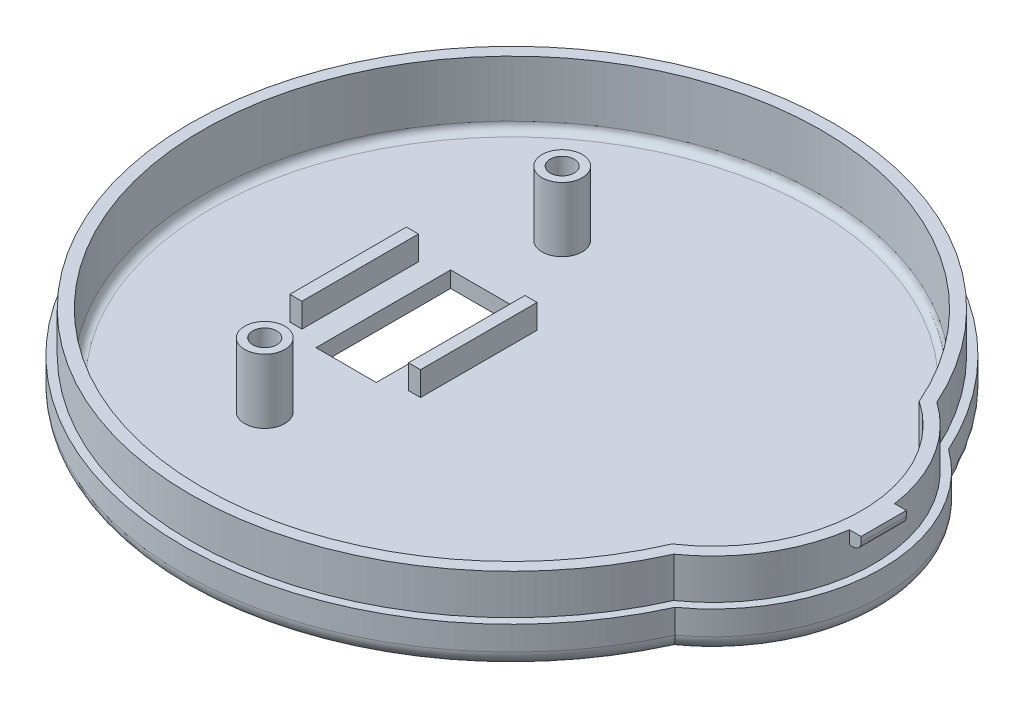
SolidWorks part; units mm, degrees
ref_plane "Front Plane" through (0, 0, 0) normal (0, 0, 1) x (1, 0, 0)
ref_plane "Top Plane" through (0, 0, 0) normal (0, 1, 0) x (1, 0, 0)
ref_plane "Right Plane" through (0, 0, 0) normal (1, 0, 0) x (0, 0, -1)
sketch "Sketch4" plane through (0, 0, 0) normal (0, 1, 0) x (1, 0, 0)
  line L0 (0, 0) -> (25, 0)
  line L1 (-47.85, 0) -> (47.85, 0) construction
  arc A0 (36.5, 16.3631) -> (36.5, -16.3631) centre (0, 0) ccw
  arc A1 (36.5, -16.3631) -> (36.5, 16.3631) centre (25, 0) ccw
  arc A2 (36.5, 16.3631) -> (5, 0) centre (25, 0) ccw construction
  arc A3 (5, 0) -> (36.5, -16.3631) centre (25, 0) ccw construction
  arc A4 (36.5, -16.3631) -> (36.5, 16.3631) centre (0, 0) ccw construction
  arc A5 (37.3, 17.0209) -> (37.3, -17.0209) centre (0, 0) ccw
  arc A6 (37.3, -17.0209) -> (37.3, 17.0209) centre (25, 0) ccw
  arc A7 (35.3, 15.3675) -> (35.3, -15.3675) centre (0, 0) ccw
  arc A8 (35.3, -15.3675) -> (35.3, 15.3675) centre (25, 0) ccw
  point P16 (0, 0)
  point P17 (0, 0)
  dimension "D1" = 80
  dimension "D2" = 40
  dimension "D3" = 25
  dimension "D4" = 1
  dimension "D5" = 2.5
extrude "Boss-Extrude3" add sketch "Sketch4" along normal blind 2 contours A7 A8 | A0 A1 A8 A7 | A5 A6 A1 A0 region at (43.8327, 0, 0) region at (45.8804, 0, 0) region at (42.3751, 0, 0)
extrude "Boss-Extrude4" add sketch "Sketch4<5>" along normal blind 10 contours A0 A1 A8 A7 region at (43.8327, 0, 0)
sketch "Sketch4<5>" plane through (0, 0, 0) normal (0, 1, 0) x (1, 0, 0) same geometry as "Sketch4"
extrude "Boss-Extrude5" add sketch "Sketch4<6>" along normal blind 5 contours A5 A6 A1 A0 region at (45.8804, 0, 0)
sketch "Sketch4<6>" plane through (0, 0, 0) normal (0, 1, 0) x (1, 0, 0) same geometry as "Sketch4"
sketch "Sketch11" plane through (0, 10, 0) normal (0, 1, 0) x (1, 0, 0)
  line L1 (43.75, -2.8061) -> (46.25, -2.8061)
  line L2 (43.75, -2.8061) -> (43.75, 2.8061)
  line L3 (43.75, 2.8061) -> (46.25, 2.8061)
  line L4 (46.25, -2.8061) -> (46.25, 2.8061)
  line L5 (43.75, -2.8061) -> (46.25, 2.8061) construction
  line L6 (43.75, 2.8061) -> (46.25, -2.8061) construction
  arc A0 (36.5, -16.3631) -> (36.5, 16.3631) centre (25, 0) ccw construction
  point P0 (45, 0)
  dimension "D1" = 2.5
extrude "Boss-Extrude7" add sketch "Sketch11" against normal blind 1.65
fillet "Fillet2" radius 1 1 edges at (46.25, 8.35, 0)
sketch "Sketch12" plane through (0, 0, 0) normal (0, -1, 0) x (1, 0, 0)
  line L0 (-41, 0) -> (-12.25, 0)
  line L1 (47.85, 0) -> (-47.85, 0) construction
  line L7 (-16, -8.375) -> (-8.5, -8.375)
  line L8 (-16, -8.375) -> (-16, 8.375)
  line L9 (-16, 8.375) -> (-8.5, 8.375)
  line L10 (-8.5, -8.375) -> (-8.5, 8.375)
  line L11 (-16, -8.375) -> (-8.5, 8.375) construction
  line L12 (-16, 8.375) -> (-8.5, -8.375) construction
  arc A0 (37.3, 17.0209) -> (37.3, -17.0209) centre (0, 0) ccw construction
  dimension "D1" = 28.75
  dimension "D2" = 16.75
  dimension "D3" = 7.5
extrude "Cut-Extrude1" cut sketch "Sketch12" against normal up to surface (2 mm away) contours L8 L9 L10 L7 up to face at (2.5, 2, 0)
sketch "Sketch15" plane through (0, 0, 0) normal (0, -1, 0) x (1, 0, 0)
  line L0 (-8.5, 8.375) -> (-10.6212, 8.375)
  line L1 (-16, 8.375) -> (-8.5, 8.375) construction
  line L2 (-10.6212, 8.375) -> (-10.6212, 13.4492)
  line L3 (-8.5, -8.375) -> (-10.6212, -8.375)
  line L4 (-16, -8.375) -> (-8.5, -8.375) construction
  line L5 (-10.6212, -8.375) -> (-10.6212, -14.2705)
  text T0 "HI" font "Century Gothic" height 3.175
  text T1 "LO"
  text T2 "OFF"
sketch "Sketch17" plane through (0, 2, 0) normal (0, 1, 0) x (1, 0, 0)
  line L2 (-8.5, 0) -> (-5.625, 0)
  line L3 (-8.5, 8.375) -> (-8.5, -8.375) construction
  line L4 (-5.625, 0) -> (-5.625, -7.25)
  line L5 (-5.625, 0) -> (-5.625, 7.25)
  line L6 (-5.625, 7.25) -> (-4.125, 7.25)
  line L7 (-4.125, 7.25) -> (-4.125, -7.25)
  line L8 (-4.125, -7.25) -> (-5.625, -7.25)
  line L9 (-16, 0) -> (-19.625, 0)
  line L10 (-16, 8.375) -> (-16, -8.375) construction
  line L12 (-20.375, -7.25) -> (-18.875, -7.25)
  line L13 (-20.375, -7.25) -> (-20.375, 7.25)
  line L14 (-20.375, 7.25) -> (-18.875, 7.25)
  line L15 (-18.875, -7.25) -> (-18.875, 7.25)
  line L16 (-20.375, -7.25) -> (-18.875, 7.25) construction
  line L17 (-20.375, 7.25) -> (-18.875, -7.25) construction
  dimension "D1" = 2.875
  dimension "D2" = 7.25
  dimension "D3" = 7.25
  dimension "D4" = 1.5
  dimension "D5" = 3.625
extrude "Boss-Extrude8" add sketch "Sketch17" along normal blind 3 contours L8 L7 L6 L5 L4 | L12 L15 L14 L13 region at (-4.875, 2, 0) region at (-20.2292, 2, 0)
sketch "Sketch18" plane through (0, 2, 0) normal (0, 1, 0) x (1, 0, 0)
  line L0 (-12.25, 8.375) -> (-12.25, 18.5)
  line L1 (-16, 8.375) -> (-8.5, 8.375) construction
  line L2 (-12.25, -8.375) -> (-12.25, -18.5)
  line L3 (-16, -8.375) -> (-8.5, -8.375) construction
  circle A0 centre (-12.25, 18.5) radius 1.5
  circle A1 centre (-12.25, -18.5) radius 1.5
  circle A2 centre (-12.25, -18.5) radius 2.5
  circle A3 centre (-12.25, 18.5) radius 2.5
  dimension "D2" = 3
  dimension "D3" = 5
  dimension "D4" = 5
  dimension "D1" = 10.125
extrude "Boss-Extrude9" add sketch "Sketch18" along normal blind 8 contours A3 A0 | A2 A1 region at (-13.9678, 2, -20.2178) region at (-10.5322, 2, 16.7822)
fillet "Fillet3" radius 2 2 edges at (-41, 0, 0) (46, 0, 0)
fillet "Fillet4" radius 1 2 edges at (43.5, 2, 0) (-38.5, 2, 0)
